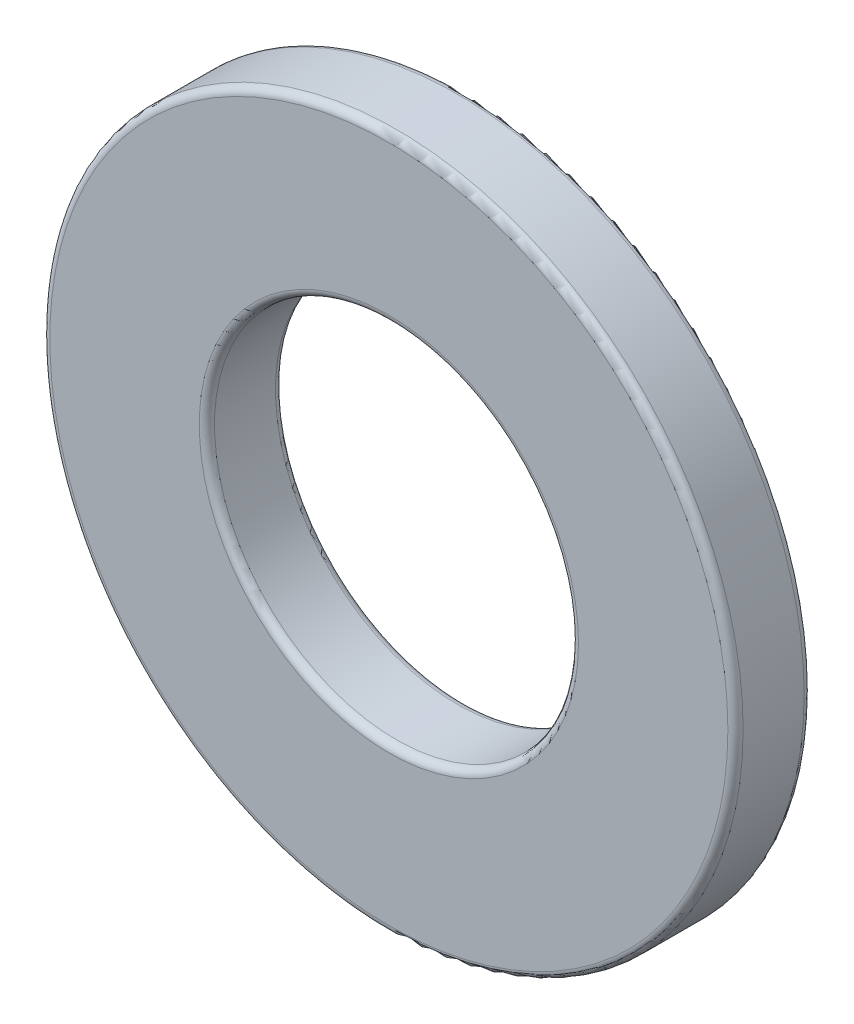
SolidWorks part; units mm, degrees
material "Alloy Steel"
ref_plane "Front Plane" through (0, 0, 0) normal (0, 0, 1) x (1, 0, 0)
ref_plane "Top Plane" through (0, 0, 0) normal (0, 1, 0) x (1, 0, 0)
ref_plane "Right Plane" through (0, 0, 0) normal (1, 0, 0) x (0, 0, -1)
sketch "Sketch1" plane through (0, 0, 0) normal (0, 0, 1) x (1, 0, 0)
  circle A0 centre (0, 0) radius 10 construction
  circle A1 centre (0, 0) radius 5.25 construction
  dimension "OD" = 20
  dimension "ID" = 10.5
sketch "Sketch2" plane through (0, 0, 0) normal (1, 0, 0) x (0, 0, -1)
  line L0 (-1.1, -10) -> (1.1, -10) construction
  point P0 (0.7, -10)
  point P4 (0, -10)
  dimension "Thickness Max" = 2.2
  dimension "Thickness Min" = 1.8
sketch "Sketch3" plane through (0, 0, 0) normal (0, 0, 1) x (1, 0, 0)
  circle A0 centre (0, 0) radius 10 construction
  circle A1 centre (0, 0) radius 10
  circle A2 centre (0, 0) radius 5.25 construction
  circle A3 centre (0, 0) radius 5.25
extrude "Boss-Extrude1" add sketch "Sketch3" against normal up to vertex (1.1 mm away) and the other way up to vertex (1.1 mm away) up to point (0, -10, -1.1) other way up to point (0, -10, 1.1)
fillet "Fillet1" radius 0.22 4 edges at (10, 0, -1.1) (5.25, 0, -1.1) (5.25, 0, 1.1) (10, 0, 1.1)
equation "\"D1@Fillet1\" = \"Thickness Max@Sketch2\" * 0.1"
